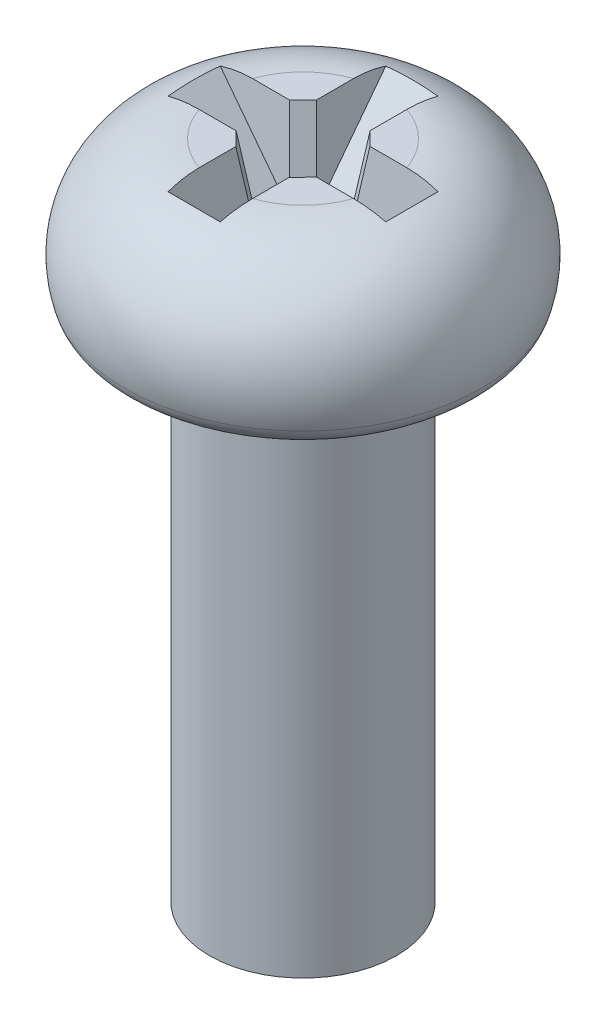
SolidWorks part; units mm, degrees
material "Plain Carbon Steel"
ref_plane "Front Plane" through (0, 0, 0) normal (0, 0, 1) x (1, 0, 0)
ref_plane "Top Plane" through (0, 0, 0) normal (0, 1, 0) x (1, 0, 0)
ref_plane "Right Plane" through (0, 0, 0) normal (1, 0, 0) x (0, 0, -1)
sketch "Sketch1" plane through (0, 0, 0) normal (0, 0, 1) x (1, 0, 0)
  line L0 (0, 9.9) -> (0, 0)
  line L1 (-1.4, 7.7) -> (-2.55, 7.7)
  line L4 (-1.4, 7.7) -> (-1.4, 0)
  line L5 (-1.4, 0) -> (0, 0)
  line L6 (0, 9.9) -> (-1.2234, 9.9)
  arc A2 (-2.55, 7.7) -> (-1.2234, 9.9) centre (-1.2234, 8.4) cw
  dimension "D1" = 2.8
  dimension "D9" = 3
  dimension "D2" = 9.9
  dimension "D3" = 5.1
  dimension "D4" = 7.7
revolve "Revolve1" add sketch "Sketch1" angle 360 about L0
fillet "Fillet1" radius 0.4 1 edges at (-2.55, 7.7, 0)
sketch "Sketch2" plane through (0, 9.9, 0) normal (0, 1, 0) x (1, 0, 0)
  line L1 (-0.4, -1.7) -> (0.4, -1.7)
  line L2 (-0.4, -1.7) -> (-0.4, 1.7)
  line L3 (-0.4, 1.7) -> (0.4, 1.7)
  line L4 (0.4, -1.7) -> (0.4, 1.7)
  line L5 (-0.4, -1.7) -> (0.4, 1.7) construction
  line L6 (-0.4, 1.7) -> (0.4, -1.7) construction
  point P0 (0, 0)
  dimension "D1" = 3.4
  dimension "D2" = 0.8
ref_plane "Plane1" through (0, 8.4, 0) normal (0, 1, 0) x (1, 0, 0)
sketch "Sketch3" plane through (0, 8.4, 0) normal (0, 1, 0) x (1, 0, 0)
  line L1 (0.2, 0.2) -> (-0.2, 0.2)
  line L2 (0.2, 0.2) -> (0.2, -0.2)
  line L3 (0.2, -0.2) -> (-0.2, -0.2)
  line L4 (-0.2, 0.2) -> (-0.2, -0.2)
  line L5 (0.2, 0.2) -> (-0.2, -0.2) construction
  line L6 (0.2, -0.2) -> (-0.2, 0.2) construction
  point P0 (0, 0)
  dimension "D1" = 0.4
loft "Cut-Loft1" cut profiles "Sketch2", "Sketch3"
pattern_circular "CirPattern1" count 2 over 90 about axis through (0, 0, 0) along (0, 1, 0) of "Cut-Loft1"
chamfer "Chamfer1" distance 0.2 angle 45 4 edges
